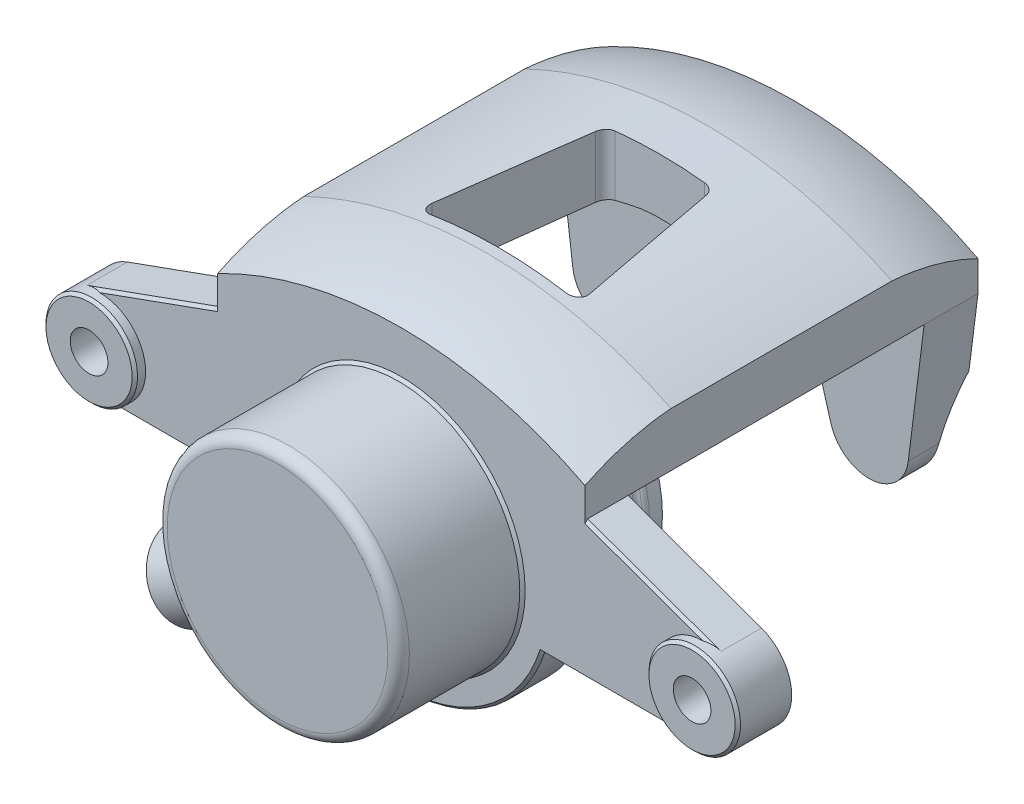
SolidWorks part; units mm, degrees
ref_plane "Płaszczyzna przednia" through (0, 0, 0) normal (0, 0, 1) x (1, 0, 0)
ref_plane "Płaszczyzna górna" through (0, 0, 0) normal (0, 1, 0) x (1, 0, 0)
ref_plane "Płaszczyzna prawa" through (0, 0, 0) normal (1, 0, 0) x (0, 0, -1)
sketch "Szkic3" plane through (0, 0, 0) normal (0, 0, 1) x (1, 0, 0)
  line L46 (-40.3579, 88.0343) -> (-42.6828, 89.5)
  line L47 (-42.6828, 89.5) -> (-44.5, 89.5)
  line L48 (-44.5, 89.5) -> (-44.5, 85.5)
  line L49 (-46.5, 83.5) -> (-48.5, 83.5)
  line L50 (-50.5, 85.5) -> (-50.5, 106.5)
  line L51 (-48.5, 108.5) -> (-46.5, 108.5)
  line L52 (-44.5, 106.5) -> (-44.5, 104.5)
  line L53 (-44.5, 104.5) -> (-43.5, 104.5)
  line L54 (-43.5, 104.5) -> (-43.5, 130)
  line L55 (-44, 130.5) -> (-50.7929, 130.5)
  line L56 (-50.7929, 130.5) -> (-57.5943, 123.6986)
  line L57 (57.5943, 123.6986) -> (50.7929, 130.5)
  line L58 (50.7929, 130.5) -> (44, 130.5)
  line L59 (43.5, 130) -> (43.5, 104.5)
  line L60 (43.5, 104.5) -> (44.5, 104.5)
  line L61 (44.5, 104.5) -> (44.5, 106.5)
  line L62 (46.5, 108.5) -> (48.5, 108.5)
  line L63 (50.5, 106.5) -> (50.5, 85.5)
  line L64 (48.5, 83.5) -> (46.5, 83.5)
  line L65 (44.5, 85.5) -> (44.5, 89.5)
  line L66 (44.5, 89.5) -> (42.6828, 89.5)
  line L67 (42.6828, 89.5) -> (40.3579, 88.0343)
  line L68 (13.6926, 80.3305) -> (-13.6926, 80.3305)
  circle A2 centre (56, 105) radius 3.5
  circle A5 centre (43, 72.2969) radius 4
  circle A6 centre (-43, 72.2969) radius 4
  circle A7 centre (-56, 105) radius 3.5
  arc A46 (-46.5, 83.5) -> (-44.5, 85.5) centre (-46.5, 85.5) ccw
  arc A47 (-50.5, 85.5) -> (-48.5, 83.5) centre (-48.5, 85.5) ccw
  arc A48 (-48.5, 108.5) -> (-50.5, 106.5) centre (-48.5, 106.5) ccw
  arc A49 (-44.5, 106.5) -> (-46.5, 108.5) centre (-46.5, 106.5) ccw
  arc A50 (-43.5, 130) -> (-44, 130.5) centre (-44, 130) ccw
  arc A51 (-57.5943, 123.6986) -> (-57.6155, 81.3412) centre (-18, 102.5) ccw
  arc A52 (-57.6155, 81.3412) -> (-50.0301, 76.524) centre (0, 163.6859) ccw
  arc A53 (-50.0301, 76.524) -> (-35.2615, 69.5752) centre (-43, 72.2969) ccw
  arc A54 (-35.2615, 69.5752) -> (35.2615, 69.5752) centre (0, 163.6859) ccw
  arc A55 (35.2615, 69.5752) -> (50.0301, 76.524) centre (43, 72.2969) ccw
  arc A56 (50.0301, 76.524) -> (57.6155, 81.3412) centre (0, 163.6859) ccw
  arc A57 (57.6155, 81.3412) -> (57.5943, 123.6986) centre (18, 102.5) ccw
  arc A58 (44, 130.5) -> (43.5, 130) centre (44, 130) ccw
  arc A59 (46.5, 108.5) -> (44.5, 106.5) centre (46.5, 106.5) ccw
  arc A60 (50.5, 106.5) -> (48.5, 108.5) centre (48.5, 106.5) ccw
  arc A61 (48.5, 83.5) -> (50.5, 85.5) centre (48.5, 85.5) ccw
  arc A62 (44.5, 85.5) -> (46.5, 83.5) centre (46.5, 85.5) ccw
  arc A63 (13.6926, 80.3305) -> (40.3579, 88.0343) centre (13.6926, 130.3305) ccw
  arc A64 (-40.3579, 88.0343) -> (-13.6926, 80.3305) centre (-13.6926, 130.3305) ccw
sketch "Szkic4" plane through (0, 0, 0) normal (0, 0, 1) x (1, 0, 0)
  line L0 (-56, 96.5) -> (-26.1534, 96.5)
  line L1 (56, 96.5) -> (26.1534, 96.5)
  line L2 (9.3304, 130.8688) -> (58.8839, 112.9958)
  line L3 (-9.3304, 130.8688) -> (-58.8839, 112.9958)
  circle A0 centre (-56, 105) radius 3.5
  circle A1 centre (56, 105) radius 3.5
  circle A2 centre (0, 105) radius 17.5
  circle A3 centre (56, 105) radius 8.5
  circle A4 centre (-56, 105) radius 8.5
  circle A5 centre (0, 105) radius 22.5
  circle A6 centre (0, 105) radius 27.5
  dimension "D1" = 35
  dimension "D2" = 5
  dimension "D3" = 5
  dimension "D4" = 10
extrude "Dodanie-wyciągnięcie1" add sketch "Szkic4" along normal blind 8 contours A6 L3 A4 L0 | A4 A0 | A6 A5 | A5 A2 | A6 L1 A3 L2 | A3 A1 region at (-36.4854, 110.0723, 0) region at (-64.1362, 103.5776, 0) region at (-24.0011, 116.7482, 0) region at (36.4854, 110.0723, 0) region at (47.8638, 106.4224, 0) region at (-21.8636, 105, 0)
extrude "Dodanie-wyciągnięcie2" add sketch "Szkic4<3>" along normal blind 2 from surface contours A4 A0 | A3 A1 region at (-64.1362, 103.5776, 0) region at (47.8638, 106.4224, 0) starting at face at (0, 106.7421, 8)
sketch "Szkic4<3>" plane through (0, 0, 0) normal (0, 0, 1) x (1, 0, 0) same geometry as "Szkic4"
ref_axis "Oś1" through (0, 105, 8) along (0, 0, -1)
sketch "Szkic6" plane through (0, 0, 0) normal (1, 0, 0) x (0, 0, -1)
  line L0 (0, 104.9333) -> (0, 87.5)
  line L1 (0, 87.5) -> (0, 122.5)
  line L2 (0, 122.5) -> (15, 122.5)
  line L3 (17, 123) -> (17, 128.5)
  line L4 (17, 128.5) -> (14.618, 128.5)
  line L5 (13.7236, 127.9472) -> (13.7764, 128.0528)
  line L6 (12.882, 127.5) -> (5.118, 127.5)
  line L7 (4.2236, 128.0528) -> (4.2764, 127.9472)
  line L8 (3.382, 128.5) -> (1, 128.5)
  line L9 (0, 130) -> (0, 104.5) construction
  line L10 (0, 128.5) -> (0, 122.5)
  line L11 (0, 129.5) -> (0, 130)
  line L12 (0, 129.5) -> (0, 122.5)
  line L13 (17, 123) -> (17, 128.5)
  line L16 (16, 123) -> (16, 123.5)
  line L17 (16, 123.5) -> (15, 123.5)
  line L18 (15, 123.5) -> (15, 122.5)
  line L20 (15, 122.5) -> (0, 122.5)
  line L21 (16, 123) -> (17, 123)
  arc A0 (14.618, 128.5) -> (13.7236, 127.9472) centre (14.618, 127.5) ccw
  arc A1 (13.7764, 128.0528) -> (12.882, 127.5) centre (12.882, 128.5) cw
  arc A2 (4.2764, 127.9472) -> (3.382, 128.5) centre (3.382, 127.5) ccw
  arc A3 (5.118, 127.5) -> (4.2236, 128.0528) centre (5.118, 128.5) cw
  arc A4 (1, 128.5) -> (0, 129.5) centre (1, 129.5) cw
  point P8 (2.191, 128.5)
  point P19 (14, 128.5)
  point P22 (13.5, 127.5)
  point P27 (4.5, 127.5)
  dimension "D7" = 1
  dimension "D2" = 3
  dimension "D4" = 5
  dimension "D5" = 6
  dimension "D6" = 9
  dimension "D9" = 1
  dimension "D10" = 1
revolve "Obrót1" add sketch "Szkic6" angle 360 about axis through (0, 105, 8) along (0, 0, -1) region at (0, 125.2877, -8.3079)
extrude "Dodanie-wyciągnięcie3" add sketch "Szkic4<5>" along normal blind 20 from surface contours A5 A2 region at (-21.8636, 105, 0) starting at face at (17.5, 105, 8)
sketch "Szkic4<5>" plane through (0, 0, 0) normal (0, 0, 1) x (1, 0, 0) same geometry as "Szkic4"
sketch "Szkic8" plane through (0, 0, 0) normal (0, 0, -1) x (-1, 0, 0)
  line L1 (-9.3304, 130.8688) -> (-58.8839, 112.9958) construction
  line L2 (9.3304, 130.8688) -> (58.8839, 112.9958) construction
  line L3 (-34.1071, 121.9323) -> (-34.1071, 131.9323)
  line L4 (34.1071, 121.9323) -> (34.1071, 131.9323)
  line L5 (34.1071, 121.9323) -> (58.8839, 112.9958)
  line L6 (-34.1071, 121.9323) -> (-58.8839, 112.9958)
  line L7 (34.1071, 121.9323) -> (5.7793, 128.8086)
  line L8 (-34.1071, 121.9323) -> (-5.7793, 128.8086)
  arc A1 (-34.1071, 131.9323) -> (34.1071, 131.9323) centre (0, 61.9323) cw
  circle A3 centre (0, 105) radius 24.5 construction
  arc A5 (5.7793, 128.8086) -> (-5.7793, 128.8086) centre (0, 105) ccw
  circle M5 centre (0, 105) radius 24.5
  line M8 (58.8839, 112.9958) -> (9.3304, 130.8688)
  arc M9 (9.3304, 130.8688) -> (-9.3304, 130.8688) centre (0, 105) ccw
  line M10 (-9.3304, 130.8688) -> (-58.8839, 112.9958)
  dimension "D1" = 10
  dimension "D3" = 10
extrude "Dodanie-wyciągnięcie4" add sketch "Szkic8" against normal up to surface (8 mm away) contours A1 L3 L4 M10 M9 M8 up to face at (0, 107.474, 8)
extrude "Dodanie-wyciągnięcie5" add sketch "Szkic8<3>" along normal blind 55 contours L6 | A1 L3 L4 M10 M9 M8 | L8 L7 M10 M5 M8 M9 region at (21.4845, 125.7512, 0) region at (33.402, 126.9323, 0)
sketch "Szkic8<3>" plane through (0, 0, 0) normal (0, 0, -1) x (-1, 0, 0) same geometry as "Szkic8"
sketch "Szkic9" plane through (0, 0, -55) normal (0, 0, -1) x (-1, 0, 0)
  line L0 (-34.1071, 121.9323) -> (-31.1543, 98.4757)
  line L1 (-16.7965, 97.3481) -> (-12.5622, 111.9642)
  line L2 (0, 34.2647) -> (0, -34.2647) construction
  line L3 (34.1071, 121.9323) -> (31.1543, 98.4757)
  line L4 (-34.1071, 131.9323) -> (-34.1071, 121.9323)
  line L5 (-34.1071, 121.9323) -> (-5.7793, 128.8086)
  line L6 (-34.1071, 121.9323) -> (-5.7793, 128.8086)
  line L7 (34.1071, 121.9323) -> (34.1071, 131.9323)
  line L8 (-34.1071, 131.9323) -> (-34.1071, 121.9323)
  line L11 (34.1071, 121.9323) -> (34.1071, 131.9323)
  line L12 (16.7965, 97.3481) -> (12.5622, 111.9642)
  line L17 (5.7793, 128.8086) -> (34.1071, 121.9323)
  line L18 (5.7793, 128.8086) -> (34.1071, 121.9323)
  arc A0 (-31.1543, 98.4757) -> (-16.7965, 97.3481) centre (-23.859, 99.3941) ccw
  arc A1 (31.1543, 98.4757) -> (16.7965, 97.3481) centre (23.859, 99.3941) cw
  arc A2 (5.7793, 128.8086) -> (-5.7793, 128.8086) centre (0, 105) ccw
  arc A3 (34.1071, 131.9323) -> (-34.1071, 131.9323) centre (0, 61.9323) ccw
  arc A5 (34.1071, 131.9323) -> (-34.1071, 131.9323) centre (0, 61.9323) ccw
  arc A6 (-12.5622, 111.9642) -> (12.5622, 111.9642) centre (0, 108.3248) cw
  arc A9 (5.7793, 128.8086) -> (-5.7793, 128.8086) centre (0, 105) ccw
  point P19 (0, 155.3258)
  line M9 (-34.1071, 131.9323) -> (-34.1071, 121.9323)
  line M13 (34.1071, 121.9323) -> (34.1071, 131.9323)
  arc M14 (34.1071, 131.9323) -> (-34.1071, 131.9323) centre (0, 61.9323) ccw
  arc M32 (-5.7793, 128.8086) -> (5.7793, 128.8086) centre (0, 105) cw
  line M40 (-34.1071, 121.9323) -> (-5.7793, 128.8086)
  line M41 (5.7793, 128.8086) -> (34.1071, 121.9323)
  dimension "D1" = 0
extrude "Dodanie-wyciągnięcie6" add sketch "Szkic9" along normal blind 10 contours L1 A6 L12 A1 L3 L0 A0 M41 M32 M40 | M14 M9 M40 M32 M41 M13 region at (19.7596, 124.6142, -55) region at (0, 131.6317, -55)
sketch "Szkic10" plane through (0, 0, 0) normal (1, 0, 0) x (0, 0, -1)
  line L0 (65, 92.0413) -> (65, 98.4757) construction
  line L1 (65, 121.9323) -> (65, 98.4757) construction
  line L2 (65, 131.9323) -> (65, 121.9323) construction
  line L3 (65, 131.9323) -> (65, 139.7995) construction
  line L4 (65, 139.7995) -> (-8, 139.7995) construction
  line L6 (-8, 121.9323) -> (-8, 131.9323) construction
  line L7 (-8, 121.9323) -> (0, 121.9323) construction
  line L8 (55, 121.9323) -> (0, 121.9323) construction
  line L9 (55, 92.0413) -> (65, 92.0413) construction
  line L10 (55, 98.4757) -> (55, 92.0413) construction
  line L11 (55, 121.9323) -> (55, 98.4757) construction
  line L12 (65, 92.0413) -> (65, 98.4757)
  line L13 (65, 121.9323) -> (65, 98.4757)
  line L14 (65, 131.9323) -> (65, 121.9323)
  line L15 (65, 131.9323) -> (65, 135.8659)
  line L18 (-8, 121.9323) -> (-8, 131.9323)
  line L19 (-8, 121.9323) -> (0, 121.9323)
  line L20 (55, 121.9323) -> (0, 121.9323)
  line L21 (55, 92.0413) -> (65, 92.0413)
  line L22 (55, 98.4757) -> (55, 92.0413)
  line L23 (55, 121.9323) -> (55, 98.4757)
  line L26 (49, 139.7995) -> (70.449, 156.548)
  line L27 (8, 139.7995) -> (-11.4125, 146.1959)
  line L28 (-11.4125, 146.1959) -> (-8, 135.8659)
  line L29 (70.449, 156.548) -> (65, 135.8659)
  arc A0 (60, 92.0413) -> (65, 108.6244) centre (90, 92.0413) cw
  arc A1 (-8, 135.8659) -> (8, 139.7995) centre (11.2578, 92.0413) cw
  arc A2 (65, 135.8659) -> (49, 139.7995) centre (45.7422, 92.0413) ccw
  dimension "D3" = 16
  dimension "D1" = 25
  dimension "D2" = 16
  dimension "D4" = 3.9336
extrude "Wytnij-wyciągnięcie1" cut sketch "Szkic10" against normal mid plane 100 contours A0 L21 L12 L13 region at (0, 98.3354, -62.985)
sketch "Szkic12" plane through (0, 0, 8) normal (0, 0, 1) x (1, 0, 0)
  arc A0 (34.1071, 131.9323) -> (-34.1071, 131.9323) centre (0, 61.9323) ccw construction
  arc A1 (34.1071, 131.9323) -> (-34.1071, 131.9323) centre (0, 61.9323) ccw
ref_axis "Oś2" through (0, 61.9323, 8) along (0, 0, -1)
revolve "Wycięcie-obrót2" cut sketch "Szkic10<13>" angle 80 mid plane about axis through (0, 61.9323, 8) along (0, 0, -1) region at (0, 144.3494, -61.6891) region at (0, 140.8624, 4.1643)
sketch "Szkic10<13>" plane through (0, 0, 0) normal (1, 0, 0) x (0, 0, -1) same geometry as "Szkic10"
ref_plane "Płaszczyzna1" through (0, 121.9323, 0) normal (0, 1, 0) x (1, 0, 0)
sketch "Szkic13" plane through (0, 121.9323, 0) normal (0, 1, 0) x (1, 0, 0)
  line L0 (-15, 10) -> (-10, 40)
  line L1 (-10, 40) -> (10, 40)
  line L2 (0, -8) -> (0, 65) construction
  line L3 (-15, 10) -> (15, 10)
  line L4 (-34.1071, -8) -> (34.1071, -8) construction
  line L5 (0, -34.2647) -> (0, 34.2647) construction
  line L6 (15, 10) -> (10, 40)
  point P11 (0, 10)
  point P12 (0, 40)
  dimension "D1" = 15
  dimension "D2" = 10
  dimension "D3" = 30
  dimension "D4" = 18
ref_plane "Płaszczyzna2" through (0, 151.9323, 0) normal (0, 1, 0) x (1, 0, 0)
sketch "Szkic15" plane through (0, 151.9323, 0) normal (0, 1, 0) x (1, 0, 0)
  line L0 (-15, 10) -> (15, 10) construction
  line L1 (15, 10) -> (10, 40) construction
  line L2 (-10, 40) -> (10, 40) construction
  line L3 (-15, 10) -> (-10, 40) construction
  line L4 (-12.6391, 10) -> (12.6391, 10)
  line L5 (14.6119, 12.3288) -> (10.2785, 38.3288)
  line L6 (-8.3057, 40) -> (8.3057, 40)
  line L7 (-14.6119, 12.3288) -> (-10.2785, 38.3288)
  arc A0 (-12.6391, 10) -> (-14.6119, 12.3288) centre (-12.6391, 12) cw
  arc A1 (12.6391, 10) -> (14.6119, 12.3288) centre (12.6391, 12) ccw
  arc A2 (10.2785, 38.3288) -> (8.3057, 40) centre (8.3057, 38) ccw
  arc A3 (-8.3057, 40) -> (-10.2785, 38.3288) centre (-8.3057, 38) ccw
  dimension "D1" = 2
extrude "Wytnij-wyciągnięcie7" cut sketch "Szkic15" against normal up to surface (25.9441 mm away) up to face at (0, 129.1543, -27.5)
sketch "Szkic16" plane through (0, 0, 28) normal (0, 0, 1) x (1, 0, 0)
  circle A0 centre (0, 105) radius 22.5
extrude "Dodanie-wyciągnięcie7" add sketch "Szkic16" along normal blind 3
sketch "Szkic19" plane through (0, 0, 28) normal (0, 0, -1) x (-1, 0, 0)
  circle A1 centre (0, 105) radius 17.5
  circle A2 centre (0, 105) radius 17.5
  dimension "D1" = 0
fillet "Zaokrąglenie1" radius 2 1 edges at (22.5, 105, 31)
chamfer "Sfazowanie1" distance 0.5 angle 45 6 edges at (22.5, 105, 8) (41.0767, 96.5, 8) (0, 77.5, 8) (-41.0767, 96.5, 8) (46.4955, 117.4641, 8) (-46.4955, 117.4641, 8)
chamfer "Sfazowanie2" distance 0.5 angle 45 2 edges at (-47.5, 105, 10) (64.5, 105, 10)
ref_plane "Płaszczyzna3" through (45.4663, 26.25, 0) normal (0.866, 0.5, 0) x (0, 0, -1)
sketch "Szkic22" plane through (45.4663, 26.25, 0) normal (0.866, 0.5, 0) x (0, 0, -1)
  line L0 (-8, 90.9327) -> (0, 90.9327) construction
  line L1 (-31, 111.4327) -> (-31, 70.4327) construction
  circle A0 centre (-21, 90.9327) radius 7.5
  dimension "D2" = 15
  dimension "D1" = 10
extrude "Dodanie-wyciągnięcie9" add sketch "Szkic22" along normal up to surface (8.7868 mm away) from offset 30 up to face at (22.5, 105, 8.5) offset against normal yes
sketch "Szkic23" plane through (19.4856, 11.25, 0) normal (-0.866, -0.5, 0) x (0, 0, 1)
  circle A0 centre (21, 90.9327) radius 6
  dimension "D1" = 12
extrude "Wytnij-wyciągnięcie9" cut sketch "Szkic23" against normal up to surface (13.5607 mm away) up to face at (17.5, 105, -15)
